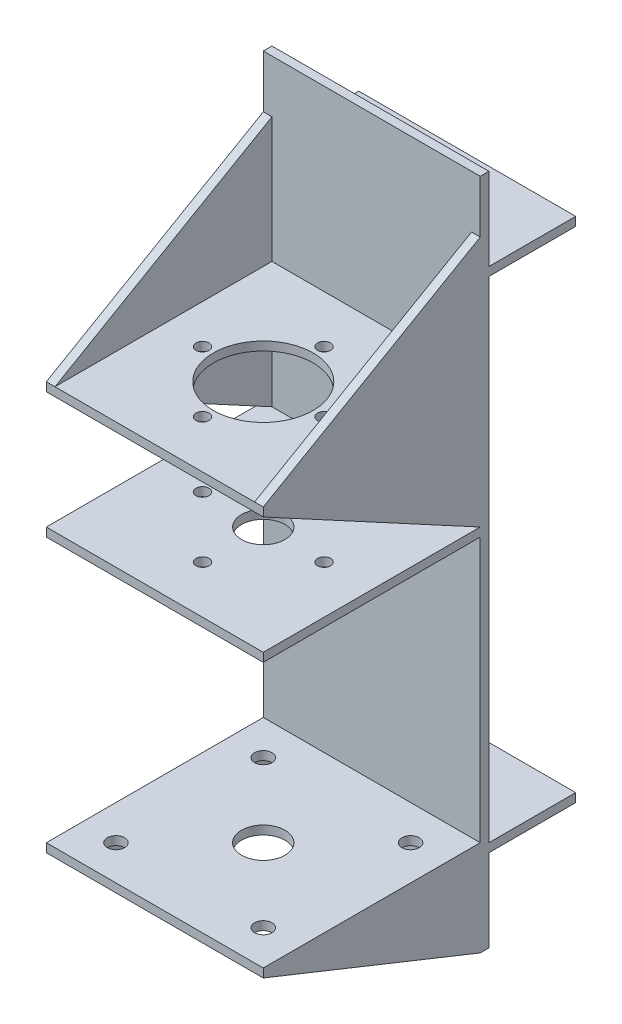
SolidWorks part; units mm, degrees
ref_plane "Front Plane" through (0, 0, 0) normal (0, 0, 1) x (1, 0, 0)
ref_plane "Top Plane" through (0, 0, 0) normal (0, 1, 0) x (1, 0, 0)
ref_plane "Right Plane" through (0, 0, 0) normal (1, 0, 0) x (0, 0, -1)
sketch "Sketch1" plane through (0, 0, 0) normal (0, 0, 1) x (1, 0, 0)
  line L1 (-25, 77.5) -> (25, 77.5)
  line L2 (-25, 77.5) -> (-25, -77.5)
  line L3 (-25, -77.5) -> (25, -77.5)
  line L4 (25, 77.5) -> (25, -77.5)
  line L5 (-25, 77.5) -> (25, -77.5) construction
  line L6 (-25, -77.5) -> (25, 77.5) construction
  point P0 (0, 0)
  dimension "D1" = 155
  dimension "D2" = 50
extrude "Boss-Extrude1" add sketch "Sketch1" along normal blind 2
sketch "Sketch2" plane through (0, 0, 2) normal (0, 0, 1) x (1, 0, 0)
  line L0 (-25, 77.5) -> (-25, -77.5) construction
  line L1 (-25, -57.5) -> (25, -57.5)
  line L2 (-25, -57.5) -> (-25, -55.5)
  line L3 (-25, -55.5) -> (25, -55.5)
  line L4 (25, -57.5) -> (25, -55.5)
  line L5 (25, -77.5) -> (25, 77.5) construction
  line L6 (-25, -77.5) -> (25, -77.5) construction
  dimension "D1" = 2
  dimension "D2" = 20
extrude "Boss-Extrude2" add sketch "Sketch2" along normal blind 50
sketch "Sketch3" plane through (0, 0, 2) normal (0, 0, 1) x (1, 0, 0)
  line L0 (-25, 77.5) -> (-25, -55.5) construction
  line L1 (-25, 5.5) -> (25, 5.5)
  line L2 (-25, 5.5) -> (-25, 7.5)
  line L3 (-25, 7.5) -> (25, 7.5)
  line L4 (25, 5.5) -> (25, 7.5)
  line L5 (25, -55.5) -> (25, 77.5) construction
  line L6 (25, 77.5) -> (-25, 77.5) construction
  dimension "D1" = 2
  dimension "D2" = 70
extrude "Boss-Extrude3" add sketch "Sketch3" along normal blind 50
sketch "Sketch4" plane through (0, -55.5, 0) normal (0, 1, 0) x (1, 0, 0)
  line L0 (-25, -52) -> (25, -2) construction
  line L1 (25, -52) -> (-25, -2) construction
  circle A1 centre (0, -27) radius 24 construction
  circle A2 centre (-16.9706, -43.9706) radius 2
  circle A3 centre (16.9706, -43.9706) radius 2
  circle A4 centre (16.9706, -10.0294) radius 2
  circle A5 centre (-16.9706, -10.0294) radius 2
  dimension "D1" = 48
  dimension "D2" = 4
extrude "Cut-Extrude1" cut sketch "Sketch4" against normal through all
ref_plane "Plane1" through (13.5, 0, 13.5) normal (0.7071, 0, 0.7071) x (0.7071, 0, -0.7071)
ref_plane "Plane2" through (-13.5, 0, 13.5) normal (-0.7071, 0, 0.7071) x (0.7071, 0, 0.7071)
ref_axis "Axis1" through (0, -94.7939, 27) along (0, 1, 0)
sketch "Sketch5" plane through (0, 7.5, 0) normal (0, 1, 0) x (1, 0, 0)
  circle A0 centre (0, -27) radius 5
  dimension "D1" = 10
extrude "Cut-Extrude2" cut sketch "Sketch5" against normal through all
sketch "Sketch6" plane through (0, 5.5, 0) normal (0, -1, 0) x (1, 0, 0)
  circle A0 centre (0, 27) radius 14 construction
  circle A1 centre (0, 41) radius 1.5
  circle A2 centre (14, 27) radius 1.5
  circle A3 centre (0, 13) radius 1.5
  circle A4 centre (-14, 27) radius 1.5
  dimension "D1" = 28
  dimension "D2" = 3
extrude "Cut-Extrude3" cut sketch "Sketch6" against normal through all
sketch "Sketch7" plane through (0, 0, 2) normal (0, 0, 1) x (1, 0, 0)
  line L0 (-25, 77.5) -> (-25, 7.5) construction
  line L1 (-25, 34.5) -> (25, 34.5)
  line L2 (-25, 34.5) -> (-25, 36.5)
  line L3 (-25, 36.5) -> (25, 36.5)
  line L4 (25, 34.5) -> (25, 36.5)
  line L5 (25, 7.5) -> (25, 77.5) construction
  line L6 (25, 77.5) -> (-25, 77.5) construction
  dimension "D1" = 2
  dimension "D2" = 41
extrude "Boss-Extrude4" add sketch "Sketch7" along normal blind 50
sketch "Sketch9" plane through (0, 36.5, 0) normal (0, 1, 0) x (1, 0, 0)
  circle A0 centre (0, -27) radius 11.5
  circle A1 centre (0, -27) radius 14 construction
  circle A2 centre (-14, -27) radius 1.5
  circle A3 centre (0, -41) radius 1.5
  circle A4 centre (14, -27) radius 1.5
  circle A5 centre (0, -13) radius 1.5
  dimension "D1" = 23
  dimension "D2" = 28
  dimension "D3" = 3
extrude "Cut-Extrude5" cut sketch "Sketch9" against normal up to next
sketch "Sketch12" plane through (-25, 0, 0) normal (-1, 0, 0) x (0, 0, 1)
  line L0 (2, 65.3675) -> (52, 36.5)
  line L1 (52, 36.5) -> (2, 36.5)
  line L2 (2, 36.5) -> (2, 65.3675)
  line L3 (2, -77.5) -> (2, -57.5)
  line L4 (2, -57.5) -> (52, -57.5)
  line L5 (52, -57.5) -> (2, -77.5)
  line L6 (2, 77.5) -> (2, 36.5) construction
  line L7 (2, 34.5) -> (52, 34.5)
  line L8 (52, 34.5) -> (2, 7.5)
  line L9 (2, 7.5) -> (2, 34.5)
  line L10 (52, 36.5) -> (2, 36.5) construction
  dimension "D1" = 30
extrude "Boss-Extrude5" add sketch "Sketch12" against normal blind 2
mirror "Mirror1" about plane through (0, 0, 0) normal (1, 0, 0) of "Boss-Extrude5"
sketch "Sketch13" plane through (0, 0, 0) normal (0, 0, -1) x (-1, 0, 0)
  line L0 (-25, 58.5) -> (25, 58.5)
  line L1 (25, 58.5) -> (25, 56.5)
  line L2 (25, 77.5) -> (25, -77.5) construction
  line L3 (25, 56.5) -> (1, 56.5)
  line L4 (1, 56.5) -> (1, -56.5)
  line L5 (1, -56.5) -> (25, -56.5)
  line L6 (25, -56.5) -> (25, -58.5)
  line L7 (25, -58.5) -> (-25, -58.5)
  line L8 (-25, -58.5) -> (-25, -56.5)
  line L9 (-25, -77.5) -> (-25, 77.5) construction
  line L10 (-25, -56.5) -> (-1, -56.5)
  line L11 (-1, -56.5) -> (-1, 56.5)
  line L12 (-1, 56.5) -> (-25, 56.5)
  line L13 (-25, 56.5) -> (-25, 58.5)
  line L14 (25, -77.5) -> (-25, -77.5) construction
  line L15 (-25, 77.5) -> (25, 77.5) construction
  dimension "D1" = 2
  dimension "D2" = 2
  dimension "D3" = 2
  dimension "D4" = 19
  dimension "D5" = 19
extrude "Boss-Extrude6" add sketch "Sketch13" along normal blind 20
